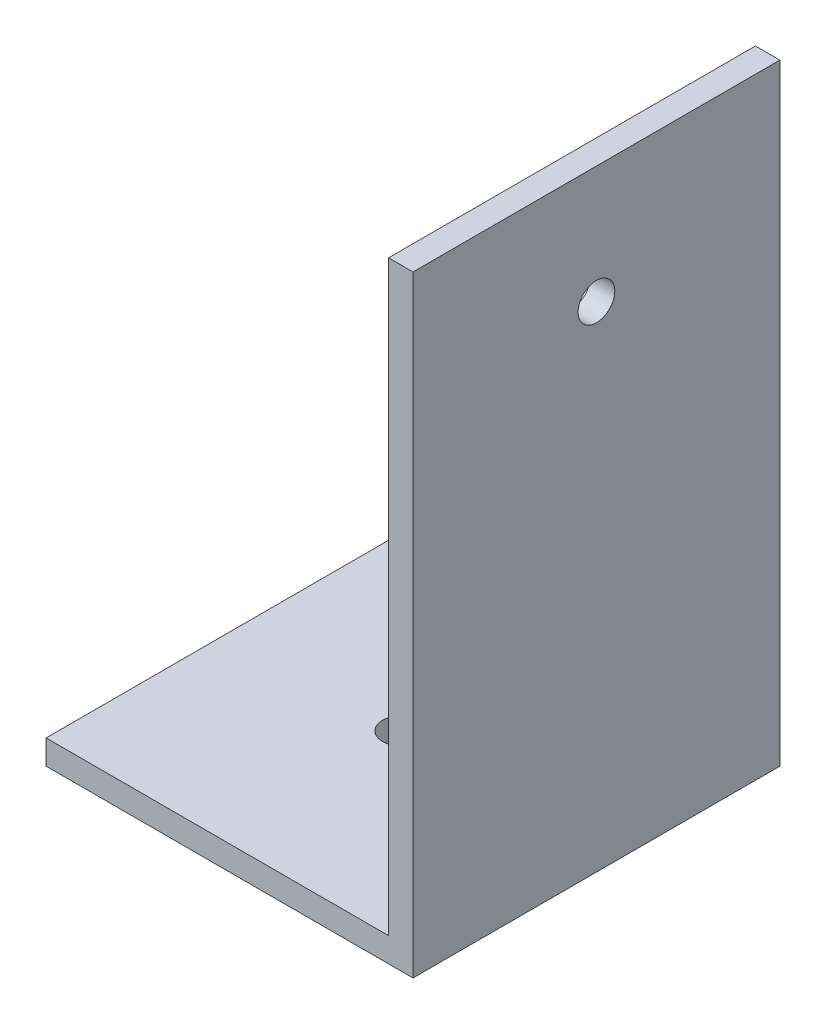
SolidWorks part; units mm, degrees
ref_plane "Piano frontale" through (0, 0, 0) normal (0, 0, 1) x (1, 0, 0)
ref_plane "Piano superiore" through (0, 0, 0) normal (0, 1, 0) x (1, 0, 0)
ref_plane "Piano destro" through (0, 0, 0) normal (1, 0, 0) x (0, 0, -1)
sketch "Schizzo1" plane through (0, 0, 0) normal (0, 0, 1) x (1, 0, 0)
  line L0 (0, 0) -> (-30, 0)
  line L1 (-30, 0) -> (-30, 2)
  line L2 (-30, 2) -> (-2, 2)
  line L3 (-2, 2) -> (-2, 50)
  line L4 (-2, 50) -> (0, 50)
  line L5 (0, 50) -> (0, 0)
  dimension "D1" = 50
  dimension "D2" = 30
  dimension "D3" = 2
extrude "Estrusione-Estrusione1" add sketch "Schizzo1" along normal blind 30
sketch "Schizzo2" plane through (-2, 0, 0) normal (-1, 0, 0) x (0, 0, 1)
  line L0 (30, 0) -> (0, 0) construction
  line L1 (15, 41.9) -> (15, 5.7333) construction
  line L2 (30, 50) -> (30, 2) construction
  line L3 (0, 50) -> (0, 2) construction
  circle A0 centre (15, 40.4) radius 1.5
  dimension "D2" = 3
  dimension "D1" = 40.4
extrude "Taglio-Estrusione1" cut sketch "Schizzo2" against normal through all
sketch "Schizzo3" plane through (0, 2, 0) normal (0, 1, 0) x (1, 0, 0)
  line L0 (-30, -15) -> (-2, -15) construction
  line L1 (-30, -30) -> (-30, 0) construction
  line L2 (-2, -30) -> (-2, 0) construction
  line L3 (-16, 0) -> (-16, -30) construction
  line L4 (-2, 0) -> (-30, 0) construction
  line L5 (-2, -30) -> (-30, -30) construction
  circle A0 centre (-16, -15) radius 1.5
  dimension "D1" = 3
extrude "Taglio-Estrusione2" cut sketch "Schizzo3" against normal through all
